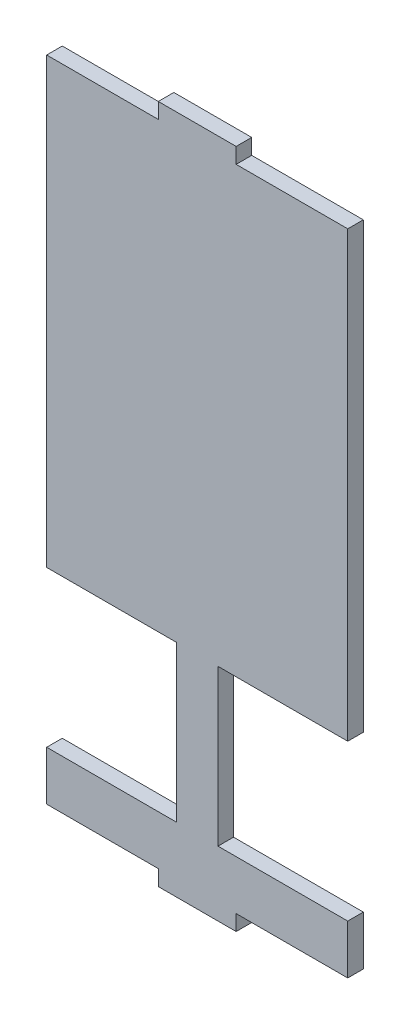
SolidWorks part; units mm, degrees
ref_plane "Plan de face" through (0, 0, 0) normal (0, 0, 1) x (1, 0, 0)
ref_plane "Plan de dessus" through (0, 0, 0) normal (0, 1, 0) x (1, 0, 0)
ref_plane "Plan de droite" through (0, 0, 0) normal (1, 0, 0) x (0, 0, -1)
sketch "Esquisse1" plane through (0, 0, 0) normal (0, 0, 1) x (1, 0, 0)
  line L0 (0, 176.8395) -> (0, -221.1538) construction
  line L1 (-58, 125) -> (58, 125)
  line L2 (-58, 125) -> (-58, -125)
  line L3 (-58, -125) -> (58, -125)
  line L4 (58, 125) -> (58, -125)
  line L5 (376.8436, 0) -> (-286.1998, 0) construction
  dimension "D1" = 250
  dimension "D2" = 116
  dimension "D3" = 58
  dimension "D4" = 125
extrude "Boss.-Extru.1" add sketch "Esquisse1" along normal blind 6
sketch "Esquisse2" plane through (0, 0, 6) normal (0, 0, 1) x (1, 0, 0)
  line L0 (-58, -125) -> (58, -125) construction
  line L1 (-15, -125) -> (15, -125)
  line L2 (-15, -125) -> (-15, -131)
  line L3 (-15, -131) -> (15, -131)
  line L4 (15, -125) -> (15, -131)
  line L5 (-58, 125) -> (-58, -125) construction
  line L6 (154.6429, 0) -> (-167.6281, 0) construction
  line L7 (15, 125) -> (15, 131)
  line L8 (-15, 131) -> (15, 131)
  line L9 (-15, 125) -> (-15, 131)
  line L10 (-15, 125) -> (15, 125)
  dimension "D1" = 6
  dimension "D2" = 30
  dimension "D3" = 43
extrude "Boss.-Extru.2" add sketch "Esquisse2" against normal blind 6
sketch "Esquisse3" plane through (0, 0, 6) normal (0, 0, 1) x (1, 0, 0)
  line L0 (58, -125) -> (58, 125) construction
  line L1 (58, -106) -> (8, -106)
  line L2 (58, -106) -> (58, -46)
  line L3 (58, -46) -> (8, -46)
  line L4 (8, -106) -> (8, -46)
  line L5 (15, -125) -> (58, -125) construction
  line L7 (0, 200.3332) -> (0, -260.5935) construction
  line L8 (-8, -106) -> (-8, -46)
  line L9 (-58, -46) -> (-8, -46)
  line L10 (-58, -106) -> (-58, -46)
  line L11 (-58, -106) -> (-8, -106)
  dimension "D1" = 50
  dimension "D2" = 60
  dimension "D3" = 19
extrude "Enlèv. mat.-Extru.1" cut sketch "Esquisse3" against normal blind 6
equation "\"D3@Esquisse1\"=\"D2@Esquisse1\"/2"
equation "\"D4@Esquisse1\"=\"D1@Esquisse1\"/2"
